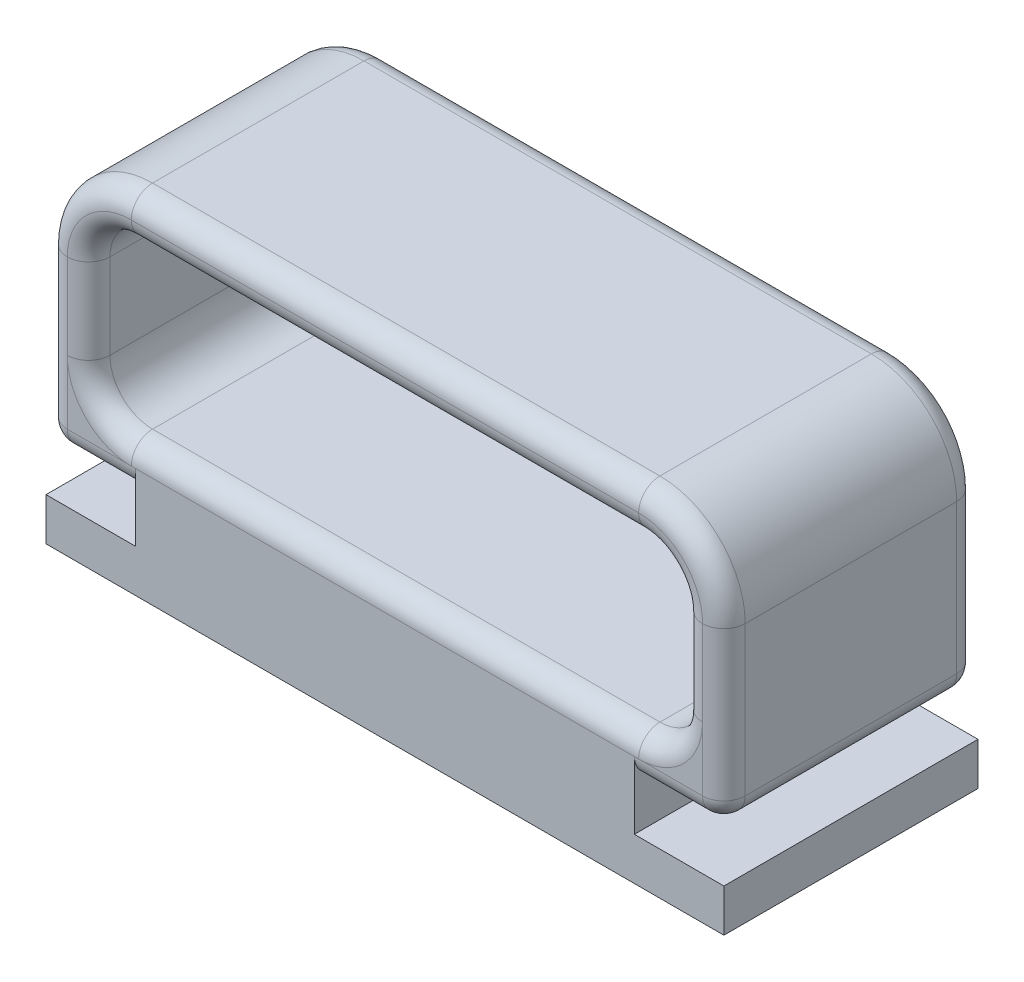
SolidWorks part; units mm, degrees
ref_plane "Спереди" through (0, 0, 0) normal (0, 0, 1) x (1, 0, 0)
ref_plane "Сверху" through (0, 0, 0) normal (0, 1, 0) x (1, 0, 0)
ref_plane "Справа" through (0, 0, 0) normal (1, 0, 0) x (0, 0, -1)
other "Configuration Table"
sketch "Эскиз1" plane through (0, 0, 0) normal (0, 0, 1) x (1, 0, 0)
  line L0 (0, 0) -> (79.5, 0)
  line L1 (79.5, 0) -> (79.5, 5)
  line L2 (79.5, 5) -> (69, 5)
  line L6 (10.5, 5) -> (0, 5)
  line L7 (0, 5) -> (0, 0)
  line L8 (10.5, 5) -> (10.5, 10.4)
  line L9 (10.5, 10.4) -> (2.5, 10.4)
  line L10 (0, 12.9) -> (0, 30.3959)
  line L11 (10, 40.3959) -> (69.5, 40.3959)
  line L12 (79.5, 30.3959) -> (79.5, 12.9)
  line L13 (77, 10.4) -> (69, 10.4)
  line L14 (69, 10.4) -> (69, 5)
  line L16 (10, 35.3959) -> (69.5, 35.3959)
  line L17 (5, 30.3959) -> (5, 20.4)
  line L18 (10, 15.4) -> (69.5, 15.4)
  line L19 (74.5, 30.3959) -> (74.5, 20.4)
  arc A0 (69.5, 40.3959) -> (79.5, 30.3959) centre (69.5, 30.3959) cw
  arc A1 (0, 30.3959) -> (10, 40.3959) centre (10, 30.3959) cw
  arc A2 (69.5, 35.3959) -> (74.5, 30.3959) centre (69.5, 30.3959) cw
  arc A3 (10, 35.3959) -> (5, 30.3959) centre (10, 30.3959) ccw
  arc A4 (69.5, 15.4) -> (74.5, 20.4) centre (69.5, 20.4) ccw
  arc A5 (5, 20.4) -> (10, 15.4) centre (10, 20.4) ccw
  arc A6 (79.5, 12.9) -> (77, 10.4) centre (77, 12.9) cw
  arc A7 (2.5, 10.4) -> (0, 12.9) centre (2.5, 12.9) cw
  point P21 (0, 40.3959)
  point P34 (0, 10.4)
  dimension "D8" = 10
  dimension "D9" = 5
  dimension "D10" = 5
  dimension "D11" = 2.5
  dimension "D1" = 79.5
  dimension "D2" = 5
  dimension "D3" = 10.5
  dimension "D4" = 5.4
  dimension "D5" = 29.9959
  dimension "D6" = 5
  dimension "D7" = 5
  dimension "D12" = 5
  dimension "D13" = 5
extrude "Бобышка-Вытянуть2" add sketch "Эскиз1" along normal blind 29.8
fillet "Скругление3" radius 2.5 34 edges at (79.5, 21.6479, 29.8) (76.5711, 37.467, 29.8) (0, 21.6479, 29.8) (2.9289, 37.467, 29.8) (79.5, 21.6479, 0) (76.5711, 37.467, 0) (0, 21.6479, 0) (2.9289, 37.467, 0) (6.4645, 16.8645, 0) (5, 25.3979, 0) (6.4645, 33.9314, 0) (39.75, 35.3959, 0) (73.0355, 33.9314, 0) (74.5, 25.3979, 0) (73.0355, 16.8645, 0) (73.0355, 33.9314, 29.8) (74.5, 25.3979, 29.8) (73.0355, 16.8645, 29.8) (39.75, 15.4, 29.8) (6.4645, 16.8645, 29.8) (5, 25.3979, 29.8) (6.4645, 33.9314, 29.8) (39.75, 40.3959, 29.8) (39.75, 40.3959, 0) (39.75, 15.4, 0) (39.75, 35.3959, 29.8) (73, 10.4, 29.8) (78.7678, 11.1322, 29.8) (6.5, 10.4, 29.8) (0.7322, 11.1322, 29.8) (73, 10.4, 0) (78.7678, 11.1322, 0) (6.5, 10.4, 0) (0.7322, 11.1322, 0)
